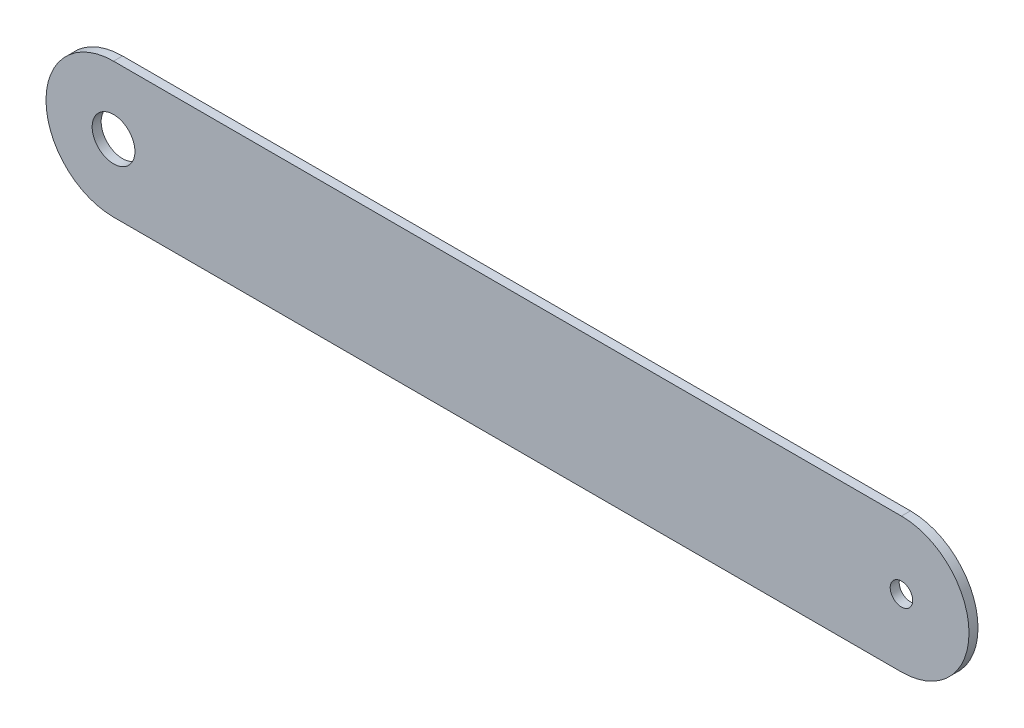
SolidWorks part; units mm, degrees
ref_plane "前视基准面" through (0, 0, 0) normal (0, 0, 1) x (1, 0, 0)
ref_plane "上视基准面" through (0, 0, 0) normal (0, 1, 0) x (1, 0, 0)
ref_plane "右视基准面" through (0, 0, 0) normal (1, 0, 0) x (0, 0, -1)
sketch "草图1" plane through (0, 0, 0) normal (0, 0, 1) x (1, 0, 0)
  line L1 (-1.4571, -0.1457) -> (348.5429, -0.1457) construction
  line L4 (348.5429, -0.1457) -> (428.5429, -0.1457) construction
  line L6 (348.5429, -30.1457) -> (-1.4571, -30.1457)
  line L7 (-1.4571, 29.8543) -> (348.5429, 29.8543)
  circle A1 centre (-1.4571, -0.1457) radius 9.5
  circle A4 centre (-1.4571, -0.1457) radius 30 construction
  circle A11 centre (348.5429, -0.1457) radius 5
  circle A14 centre (348.5429, -0.1457) radius 30 construction
  arc A17 (-1.4571, -30.1457) -> (-1.4571, 29.8543) centre (-1.4571, -0.1457) cw
  arc A18 (348.5429, 29.8543) -> (348.5429, -30.1457) centre (348.5429, -0.1457) cw
  dimension "D1" = 350
  dimension "D2" = 19
  dimension "D4" = 10
  dimension "D7" = 80
extrude "凸台-拉伸1" add sketch "草图1" along normal blind 4
